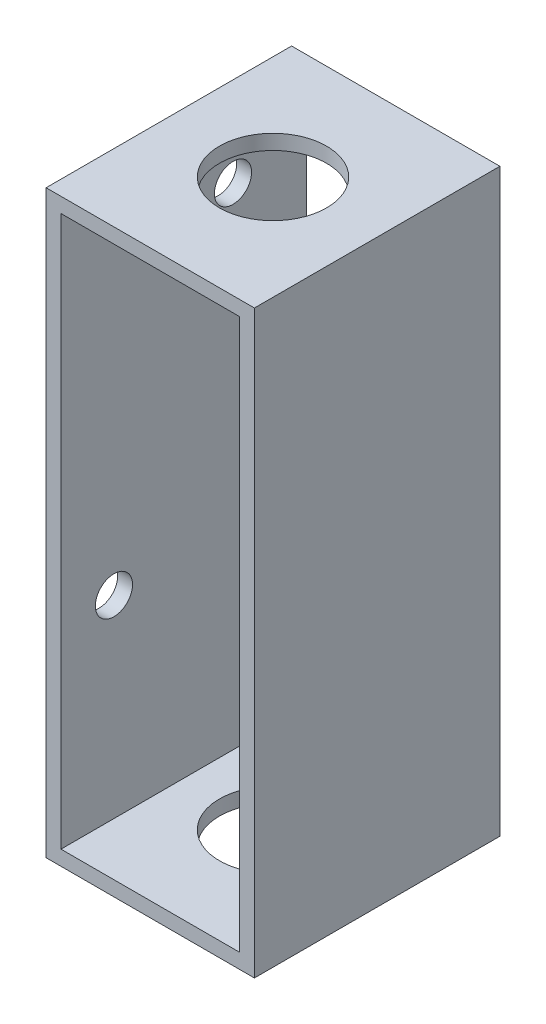
SolidWorks part; units mm, degrees
ref_plane "Front Plane" through (0, 0, 0) normal (0, 0, 1) x (1, 0, 0)
ref_plane "Top Plane" through (0, 0, 0) normal (0, 1, 0) x (1, 0, 0)
ref_plane "Right Plane" through (0, 0, 0) normal (1, 0, 0) x (0, 0, -1)
sketch "Sketch1" plane through (0, 0, 0) normal (0, 0, 1) x (1, 0, 0)
  line L1 (0, -9) -> (14, -9)
  line L2 (0, -9) -> (0, 30)
  line L3 (0, 30) -> (14, 30)
  line L4 (14, -9) -> (14, 30)
  dimension "D1" = 39
  dimension "D2" = 14
extrude "Boss-Extrude1" add sketch "Sketch1" along normal blind 16.5
sketch "Sketch3" plane through (0, 0, 0) normal (0, 0, 1) x (1, 0, 0)
  line L1 (0, 30) -> (14, 30)
  line L2 (0, 30) -> (0, -9)
  line L3 (0, -9) -> (14, -9)
  line L4 (14, 30) -> (14, -9)
  line L8 (1, 29) -> (13, 29)
  line L9 (13, 29) -> (13, -8)
  line L10 (1, -8) -> (13, -8)
  line L11 (1, 29) -> (1, -8)
  dimension "D1" = 1
extrude "Cut-Extrude3" cut sketch "Sketch3" against normal through all and the other way through all flip side to cut
sketch "Sketch4" plane through (0, 0, 0) normal (0, 1, 0) x (1, 0, 0)
  line L0 (0, -16.5) -> (14, 0) construction
  line L1 (0, 0) -> (7, -8.25) construction
  circle A0 centre (7, -8.25) radius 3.6
  point P7 (0, 0)
  dimension "D1" = 7.2
extrude "Cut-Extrude4" cut sketch "Sketch4" along direction (0, -1, 0) on the side against the normal blind 40.5 and the other way through all
sketch "Sketch5" plane through (0, 0, 0) normal (1, 0, 0) x (0, 0, -1)
  line L0 (-16.5, 30) -> (0, 30) construction
  circle A0 centre (-4.9397, 25) radius 1.25
  circle A1 centre (-12.9397, 5) radius 1.25
  dimension "D4" = 2.5
  dimension "D5" = 2.5
  dimension "D1" = 5
  dimension "D2" = 8
  dimension "D3" = 20
extrude "Cut-Extrude6" cut sketch "Sketch5" along direction (-1, 0, 0) on the side of the normal up to surface (1 mm away) up to face at (1, 10.5, 8.25)
ref_plane "Plane1" through (13, 29, 16.5) normal (-1, 0, 0) x (0, 0, 1)
